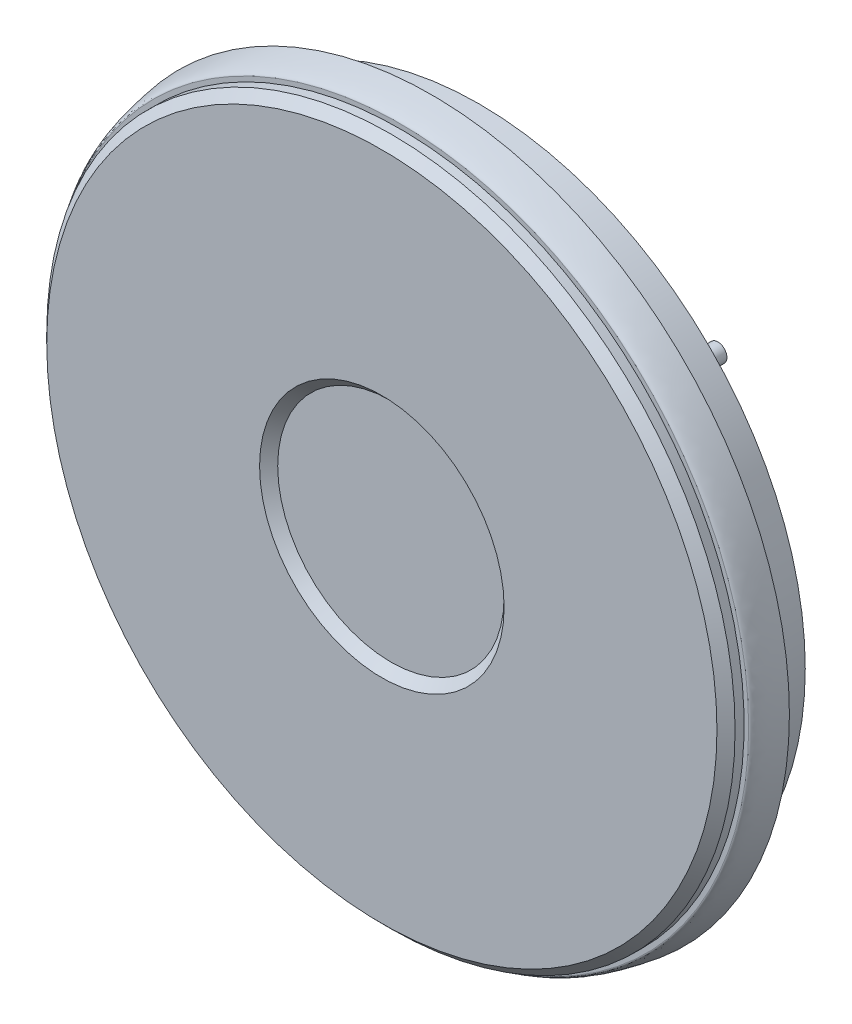
SolidWorks part; units mm, degrees
ref_plane "Front Plane" through (0, 0, 0) normal (0, 0, 1) x (1, 0, 0)
ref_plane "Top Plane" through (0, 0, 0) normal (0, 1, 0) x (1, 0, 0)
ref_plane "Right Plane" through (0, 0, 0) normal (1, 0, 0) x (0, 0, -1)
sketch "Sketch1" plane through (0, 0, 0) normal (0, 0, 1) x (1, 0, 0)
  circle A0 centre (0, 0) radius 76
  dimension "D1" = 152
extrude "Boss-Extrude1" add sketch "Sketch1" along normal blind 4
chamfer "Chamfer1" distance 2 angle 45 1 edges at (76, 0, 4)
sketch "Sketch2" plane through (0, 0, 4) normal (0, 0, 1) x (1, 0, 0)
  circle A0 centre (0, 0) radius 25
  dimension "D1" = 50
extrude "Cut-Extrude1" cut sketch "Sketch2" against normal blind 2
chamfer "Chamfer2" distance 2 angle 45 1 edges at (25, 0, 4)
sketch "Sketch3" plane through (0, 0, 0) normal (0, 1, 0) x (1, 0, 0)
  line L0 (0, 0) -> (0, 19)
  line L1 (-76, 0) -> (-76, -2) construction
  line L2 (76, 0) -> (-76, 0) construction
  line L3 (-77, 0) -> (0, 0)
  line L4 (0, 19) -> (-32, 19)
  line L5 (-69.5, 17.5) -> (-72, 17.5)
  line L6 (-72, 17.5) -> (-72, 7)
  line L7 (-72, 7) -> (-79, 7)
  line L8 (-74, -4) -> (74, -4) construction
  line L9 (-32, 19) -> (-50.5, 15.5)
  line L10 (-50.5, 15.5) -> (-57.5, 10)
  line L11 (-57.5, 10) -> (-69.5, 10)
  line L12 (-69.5, 10) -> (-69.5, 17.5)
  spline S0 degree 2 poles (-79, 7) (-77.9385, 0) (-77, 0) knots 0 0 0 1 1 1
  dimension "D1" = 2.5
  dimension "D2" = 72
  dimension "D3" = 21.5
  dimension "D4" = 79
  dimension "D5" = 11
  dimension "D6" = 1
  dimension "D7" = 10
  dimension "D8" = 23
  dimension "D9" = 32
  dimension "D10" = 12
  dimension "D11" = 7
  dimension "D12" = 3.5
  dimension "D13" = 72
revolve "Revolve1" add sketch "Sketch3" angle 360 about L0
sketch "Sketch5" plane through (0, 0, 0) normal (0, 1, 0) x (1, 0, 0)
  line L0 (0, 19) -> (-5.5, 19)
  line L1 (32, 19) -> (-32, 19) construction
  line L2 (-5.5, 19) -> (-5.5, 23)
  line L3 (-5.5, 23) -> (-3, 23)
  line L4 (-3, 23) -> (-3, 51)
  line L5 (-3, 51) -> (0, 51)
  line L6 (0, 51) -> (0, 19)
  line L7 (-74, -4) -> (74, -4) construction
  dimension "D1" = 27
  dimension "D2" = 5.5
  dimension "D3" = 3
  dimension "D4" = 28
revolve "Revolve2" add sketch "Sketch5" angle 360 about L6
sketch "Sketch6" plane through (0, 0, -7) normal (0, 0, -1) x (-1, 0, 0)
  line L0 (0, 0) -> (0, 57.5) construction
  circle A0 centre (-29.2, 27.3379) radius 2
  circle A1 centre (0, 0) radius 57.5 construction
  circle A2 centre (29.2, 27.3379) radius 2
  dimension "D1" = 4
  dimension "D2" = 58.4
  dimension "D3" = 40
extrude "Boss-Extrude2" add sketch "Sketch6" along normal offset from surface (34 mm away) 45 up to face at (27, 0, 4)
